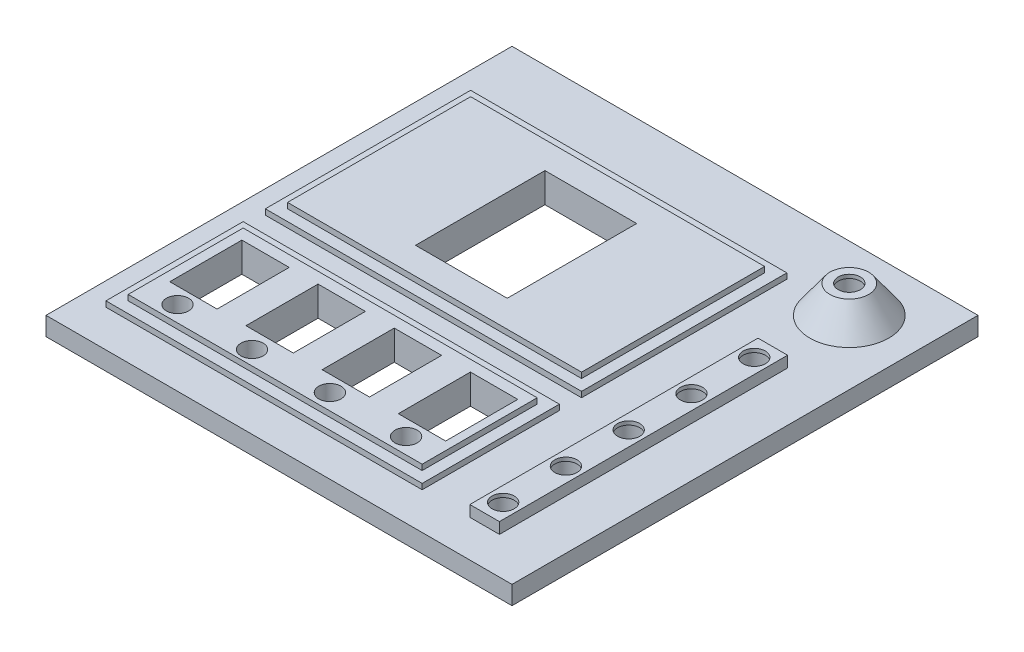
SolidWorks part; units mm, degrees
ref_plane "Front Plane" through (0, 0, 0) normal (0, 0, 1) x (1, 0, 0)
ref_plane "Top Plane" through (0, 0, 0) normal (0, 1, 0) x (1, 0, 0)
ref_plane "Right Plane" through (0, 0, 0) normal (1, 0, 0) x (0, 0, -1)
sketch "Sketch1" plane through (0, 0, 0) normal (0, 1, 0) x (1, 0, 0)
  line L1 (0, 0) -> (126, 0)
  line L2 (0, 0) -> (0, 126)
  line L3 (0, 126) -> (126, 126)
  line L4 (126, 0) -> (126, 126)
  dimension "D1" = 126
  dimension "D2" = 126
extrude "Boss-Extrude1" add sketch "Sketch1" along normal blind 5
sketch "Sketch3" plane through (0, 5, 0) normal (0, 1, 0) x (1, 0, 0)
  line L0 (108.6, 121.1) -> (108.6, 96.1) construction
  circle A0 centre (108.6, 108.6) radius 12.5
extrude "Boss-Extrude2" add sketch "Sketch3" along normal blind 7.5
sketch "Sketch4" plane through (0, 0, 0) normal (0, -1, 0) x (1, 0, 0)
  circle A1 centre (108.6, -108.6) radius 3.45
  dimension "D1" = 6.9
extrude "Cut-Extrude1" cut sketch "Sketch4" against normal blind 11.5
sketch "Sketch6" plane through (0, 12.5, 0) normal (0, 1, 0) x (1, 0, 0)
  line L0 (108.6, 121.1) -> (108.6, 96.1) construction
  circle A0 centre (108.6, 108.6) radius 12.5 construction
  circle A1 centre (108.6, 108.6) radius 3
  dimension "D1" = 6
extrude "Cut-Extrude2" cut sketch "Sketch6" against normal through all
chamfer "Chamfer1" distance 10 angle 36 1 edges at (108.6, 12.5, -96.1) first distance on face at (108.6, 12.5, -96.1)
sketch "Sketch7" plane through (0, 5, 0) normal (0, 1, 0) x (1, 0, 0)
  line L1 (0, 0) -> (126, 0) construction
  line L11 (108.6, 97.9164) -> (108.6, 0) construction
  line L12 (112.6, 10) -> (104.6, 10)
  line L13 (112.6, 10) -> (112.6, 87.9164)
  line L14 (112.6, 87.9164) -> (104.6, 87.9164)
  line L15 (104.6, 10) -> (104.6, 87.9164)
  line L16 (112.6, 10) -> (104.6, 87.9164) construction
  line L17 (112.6, 87.9164) -> (104.6, 10) construction
  circle A0 centre (108.6, 108.6) radius 10.6836 construction
  point P0 (108.6, 48.9582)
  dimension "D3" = 8
extrude "Boss-Extrude3" add sketch "Sketch7" along normal blind 3
sketch "Sketch8" plane through (0, 8, 0) normal (0, 1, 0) x (1, 0, 0)
  line L0 (108.6, 87.9164) -> (108.6, 10) construction
  line L1 (112.6, 87.9164) -> (104.6, 87.9164) construction
  line L2 (104.6, 10) -> (112.6, 10) construction
  line L9 (112.6, 87.9164) -> (104.6, 87.9164)
  line L10 (112.6, 87.9164) -> (112.6, 85.9164)
  line L12 (104.6, 87.9164) -> (104.6, 85.9164)
  circle A0 centre (108.6, 15) radius 3
  circle A1 centre (108.6, 31.9748) radius 3
  circle A2 centre (108.6, 48.9496) radius 3
  circle A3 centre (108.6, 65.9244) radius 3
  circle A4 centre (108.6, 82.8992) radius 3
  dimension "D3" = 6
  dimension "D1" = 5
  dimension "D2" = 2
extrude "Cut-Extrude3" cut sketch "Sketch8" against normal through all contours A4 | A3 | A2 | A1 | A0
sketch "Sketch9" plane through (0, 0, 0) normal (0, -1, 0) x (1, 0, 0)
  line L0 (108.6, -85.8992) -> (108.6, -12) construction
  circle A0 centre (108.6, -82.8992) radius 3 construction
  circle A1 centre (108.6, -15) radius 3 construction
  circle A2 centre (108.6, -82.8992) radius 3.45
  circle A3 centre (108.6, -65.9244) radius 3.45
  circle A4 centre (108.6, -48.9496) radius 3.45
  circle A5 centre (108.6, -15) radius 3.45
  circle A6 centre (108.6, -31.9748) radius 3.45
  dimension "D1" = 6.9
  dimension "D2" = 6.9
  dimension "D3" = 6.9
  dimension "D4" = 6.9
  dimension "D5" = 6.9
extrude "Cut-Extrude4" cut sketch "Sketch9" against normal blind 7
sketch "Sketch10" plane through (0, 5, 0) normal (0, 1, 0) x (1, 0, 0)
  line L0 (97.9164, 108.6) -> (0, 108.6) construction
  line L1 (0, 126) -> (0, 0) construction
  line L2 (104.6, 10) -> (0, 10) construction
  line L3 (48.9582, 108.6) -> (48.9582, 10) construction
  line L4 (85.7082, 31.55) -> (12.2082, 31.55)
  line L5 (48.9582, 41.1) -> (48.9582, 22)
  line L6 (12.2082, 31.0467) -> (6.2082, 31.0467) construction
  line L7 (85.7082, 41.1) -> (12.2082, 41.1)
  line L8 (85.7082, 41.1) -> (85.7082, 22)
  line L9 (85.7082, 22) -> (12.2082, 22)
  line L10 (12.2082, 41.1) -> (12.2082, 22)
  line L11 (85.7082, 41.1) -> (12.2082, 22) construction
  line L12 (85.7082, 22) -> (12.2082, 41.1) construction
  line L13 (16.976, 41.1) -> (16.976, 47.1) construction
  line L14 (85.7082, 27.9598) -> (91.7082, 27.9598) construction
  line L15 (6.2082, 47.1) -> (91.7082, 47.1)
  line L16 (6.2082, 47.1) -> (6.2082, 10)
  line L17 (6.2082, 10) -> (91.7082, 10)
  line L18 (91.7082, 47.1) -> (91.7082, 10)
  line L19 (85.7082, 22) -> (85.7082, 10) construction
  line L20 (78.5304, 41.1) -> (78.5304, 47.1) construction
  line L21 (37.839, 53.1) -> (37.839, 47.1) construction
  line L22 (91.7082, 53.1) -> (6.2082, 53.1)
  line L23 (91.7082, 53.1) -> (91.7082, 108.6)
  line L24 (91.7082, 108.6) -> (6.2082, 108.6)
  line L25 (6.2082, 53.1) -> (6.2082, 108.6)
  circle A0 centre (108.6, 108.6) radius 10.6836 construction
  point P12 (48.9582, 31.55)
  point P15 (48.9582, 31.55)
  point P18 (48.9582, 31.55)
  dimension "D1" = 73.5
  dimension "D2" = 19.1
  dimension "D3" = 6
  dimension "D4" = 6
  dimension "D5" = 6
  dimension "D6" = 12
  dimension "D7" = 6
  dimension "D8" = 6
extrude "Boss-Extrude5" add sketch "Sketch10" along normal blind 1.5 contours L25 L22 L23 L24 | L18 L15 L16 L17 L10 L7 L8 L9 | L4 L10 L9 L5 | L7 L10 L4 L5 | L8 L7 L5 L4 | L9 L8 L4 L5 region at (67.3332, 5, -26.775) region at (67.3332, 5, -36.325) region at (30.5832, 5, -26.775) region at (30.5832, 5, -36.325) region at (48.9582, 5, -46.168) region at (48.9582, 5, -80.85)
sketch "Sketch12" plane through (0, 6.5, 0) normal (0, 1, 0) x (1, 0, 0)
  line L0 (48.9582, 108.6) -> (48.9582, 53.1) construction
  line L1 (91.7082, 108.6) -> (6.2082, 108.6) construction
  line L2 (91.7082, 53.1) -> (6.2082, 53.1) construction
  line L3 (15.0136, 108.6) -> (15.0136, 105.6) construction
  line L4 (88.7082, 105.6) -> (9.2082, 105.6)
  line L5 (88.7082, 105.6) -> (88.7082, 56.1)
  line L6 (88.7082, 56.1) -> (9.2082, 56.1)
  line L7 (9.2082, 105.6) -> (9.2082, 56.1)
  line L8 (88.7082, 105.6) -> (9.2082, 56.1) construction
  line L9 (88.7082, 56.1) -> (9.2082, 105.6) construction
  line L10 (6.2082, 97.6663) -> (9.2082, 97.6663) construction
  line L11 (6.2082, 53.1) -> (6.2082, 108.6) construction
  line L12 (88.7082, 94.5303) -> (91.7082, 94.5303) construction
  line L13 (91.7082, 53.1) -> (91.7082, 108.6) construction
  line L14 (84.0877, 56.1) -> (84.0877, 53.1) construction
  point P6 (48.9582, 80.85)
  dimension "D1" = 3
  dimension "D2" = 3
extrude "Boss-Extrude6" add sketch "Sketch12" along normal blind 1.5
sketch "Sketch13" plane through (0, 6.5, 0) normal (0, 1, 0) x (1, 0, 0)
  line L0 (48.9582, 47.1) -> (48.9582, 10) construction
  line L1 (6.2082, 47.1) -> (91.7082, 47.1) construction
  line L2 (6.2082, 10) -> (91.7082, 10) construction
  line L3 (9.2082, 39.8843) -> (6.2082, 39.8843) construction
  line L4 (88.7082, 44.1) -> (9.2082, 44.1)
  line L5 (88.7082, 44.1) -> (88.7082, 13)
  line L6 (88.7082, 13) -> (9.2082, 13)
  line L7 (9.2082, 44.1) -> (9.2082, 13)
  line L8 (88.7082, 44.1) -> (9.2082, 13) construction
  line L9 (88.7082, 13) -> (9.2082, 44.1) construction
  line L10 (6.2082, 47.1) -> (6.2082, 10) construction
  line L11 (13.5806, 44.1) -> (13.5806, 47.1) construction
  line L12 (84.6207, 13) -> (84.6207, 10) construction
  line L13 (88.7082, 16.7725) -> (91.7082, 16.7725) construction
  line L14 (91.7082, 47.1) -> (91.7082, 10) construction
  point P6 (48.9582, 28.55)
  dimension "D1" = 3
  dimension "D2" = 3
  dimension "D3" = 3
  dimension "D4" = 3
extrude "Boss-Extrude7" add sketch "Sketch13" along normal blind 1.5
sketch "Sketch14" plane through (0, 8, 0) normal (0, 1, 0) x (1, 0, 0)
  line L0 (48.9582, 105.6) -> (48.9582, 56.1) construction
  line L1 (88.7082, 105.6) -> (9.2082, 105.6) construction
  line L2 (9.2082, 56.1) -> (88.7082, 56.1) construction
  line L4 (61.3582, 98.35) -> (36.5582, 98.35)
  line L5 (61.3582, 98.35) -> (61.3582, 63.35)
  line L6 (61.3582, 63.35) -> (36.5582, 63.35)
  line L7 (36.5582, 98.35) -> (36.5582, 63.35)
  line L8 (61.3582, 98.35) -> (36.5582, 63.35) construction
  line L9 (61.3582, 63.35) -> (36.5582, 98.35) construction
  point P6 (48.9582, 80.85)
  dimension "D1" = 35
  dimension "D2" = 24.8
extrude "Cut-Extrude5" cut sketch "Sketch14" against normal through all
sketch "Sketch15" plane through (0, 8, 0) normal (0, 1, 0) x (1, 0, 0)
  line L12 (49.1621, 31.35) -> (45.2621, 31.35) construction
  line L13 (49.1621, 31.35) -> (53.0621, 31.35) construction
  line L14 (45.2621, 31.35) -> (32.4621, 31.35) construction
  line L15 (53.0621, 31.35) -> (65.8621, 31.35) construction
  line L16 (32.4621, 31.35) -> (24.6621, 31.35) construction
  line L17 (65.8621, 31.35) -> (73.6621, 31.35) construction
  line L18 (24.6621, 31.35) -> (11.8621, 31.35) construction
  line L19 (73.6621, 31.35) -> (86.4621, 31.35) construction
  line L21 (45.2621, 41.1) -> (32.4621, 41.1)
  line L22 (45.2621, 41.1) -> (45.2621, 21.6)
  line L23 (45.2621, 21.6) -> (32.4621, 21.6)
  line L24 (32.4621, 41.1) -> (32.4621, 21.6)
  line L25 (45.2621, 41.1) -> (32.4621, 21.6) construction
  line L26 (45.2621, 21.6) -> (32.4621, 41.1) construction
  line L27 (24.6621, 41.1) -> (11.8621, 41.1)
  line L28 (24.6621, 41.1) -> (24.6621, 21.6)
  line L29 (24.6621, 21.6) -> (11.8621, 21.6)
  line L30 (11.8621, 41.1) -> (11.8621, 21.6)
  line L31 (24.6621, 41.1) -> (11.8621, 21.6) construction
  line L32 (24.6621, 21.6) -> (11.8621, 41.1) construction
  line L33 (65.8621, 41.1) -> (53.0621, 41.1)
  line L34 (65.8621, 41.1) -> (65.8621, 21.6)
  line L35 (65.8621, 21.6) -> (53.0621, 21.6)
  line L36 (53.0621, 41.1) -> (53.0621, 21.6)
  line L37 (65.8621, 41.1) -> (53.0621, 21.6) construction
  line L38 (65.8621, 21.6) -> (53.0621, 41.1) construction
  line L39 (86.4621, 41.1) -> (73.6621, 41.1)
  line L40 (86.4621, 41.1) -> (86.4621, 21.6)
  line L41 (86.4621, 21.6) -> (73.6621, 21.6)
  line L42 (73.6621, 41.1) -> (73.6621, 21.6)
  line L43 (86.4621, 41.1) -> (73.6621, 21.6) construction
  line L44 (86.4621, 21.6) -> (73.6621, 41.1) construction
  point P29 (38.8621, 31.35)
  point P34 (18.2621, 31.35)
  point P39 (59.4621, 31.35)
  point P44 (80.0621, 31.35)
  dimension "D6" = 3.9
  dimension "D7" = 3.9
  dimension "D8" = 12.8
  dimension "D9" = 12.8
  dimension "D10" = 7.8
  dimension "D11" = 7.8
  dimension "D12" = 12.8
  dimension "D13" = 12.8
  dimension "D14" = 19.5
  dimension "D15" = 19.5
  dimension "D16" = 19.5
  dimension "D17" = 19.5
extrude "Cut-Extrude6" cut sketch "Sketch15" against normal through all
sketch "Sketch16" plane through (0, 8, 0) normal (0, 1, 0) x (1, 0, 0)
  line L0 (18.2621, 21.6) -> (18.2621, 13) construction
  line L1 (11.8621, 21.6) -> (24.6621, 21.6) construction
  line L2 (9.2082, 13) -> (88.7082, 13) construction
  line L3 (38.8621, 21.6) -> (38.8621, 13) construction
  line L4 (32.4621, 21.6) -> (45.2621, 21.6) construction
  line L5 (59.4621, 21.6) -> (59.4621, 13) construction
  line L6 (53.0621, 21.6) -> (65.8621, 21.6) construction
  line L7 (80.0621, 21.6) -> (80.0621, 13) construction
  line L8 (73.6621, 21.6) -> (86.4621, 21.6) construction
  circle A0 centre (18.2621, 17.3) radius 3
  circle A1 centre (38.8621, 16.8484) radius 3
  circle A2 centre (59.4621, 17.3) radius 3
  circle A3 centre (80.0621, 17.3) radius 3
  dimension "D1" = 6
  dimension "D2" = 6
  dimension "D3" = 6
  dimension "D4" = 6
extrude "Cut-Extrude7" cut sketch "Sketch16" against normal through all
